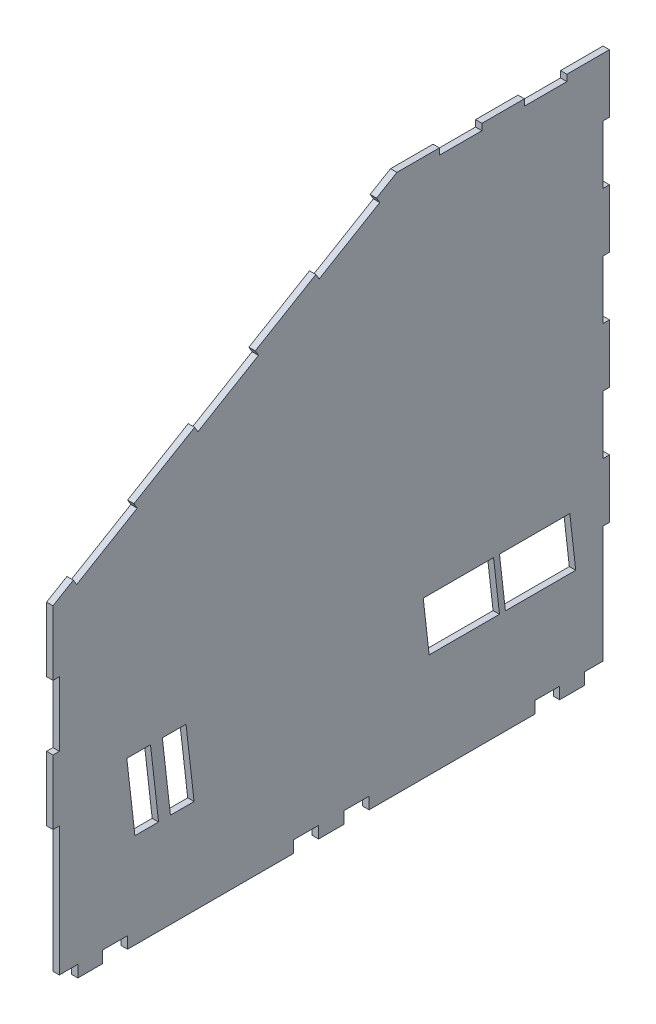
SolidWorks part; units mm, degrees
ref_plane "Ön Düzlem" through (0, 0, 0) normal (0, 0, 1) x (1, 0, 0)
ref_plane "Üst Düzlem" through (0, 0, 0) normal (0, 1, 0) x (1, 0, 0)
ref_plane "Sağ Düzlem" through (0, 0, 0) normal (1, 0, 0) x (0, 0, -1)
sketch "Sketch1" plane through (0, 0, 0) normal (1, 0, 0) x (0, 0, -1)
  line L0 (117.52, 112.5) -> (99.566, 112.5)
  line L13 (-107.0133, -112.5) -> (-107.0133, -114.8)
  line L14 (-6.4686, 92.2661) -> (-32.0795, 77.122)
  line L17 (27.75, 112.5) -> (19.1423, 107.4101)
  line L18 (-114.82, -109.8) -> (-107.0133, -109.8)
  line L20 (-107.0133, -114.8) -> (-96.5067, -114.8)
  line L21 (-86, -112.5) -> (-86, -114.8)
  line L22 (-114.82, -27.96) -> (-114.82, -0.68)
  line L23 (-117.52, -55.24) -> (-117.52, -27.96)
  line L24 (-96.5067, -114.8) -> (-96.5067, -112.5)
  line L25 (-117.52, -0.68) -> (-117.52, 26.6)
  line L26 (-117.52, -0.68) -> (-114.82, -0.68)
  line L27 (-117.52, -27.96) -> (-114.82, -27.96)
  line L28 (-114.82, -82.52) -> (-114.82, -55.24)
  line L29 (-117.52, -55.24) -> (-114.82, -55.24)
  line L31 (-86, -109.8) -> (-86, -112.5)
  line L32 (-107.0133, -109.8) -> (-107.0133, -112.5)
  line L33 (-96.5067, -109.8) -> (-96.5067, -112.5)
  line L34 (-96.5067, -109.8) -> (-86, -109.8)
  line L35 (-5.3333, -112.5) -> (-5.3333, -114.8)
  line L37 (-16, -112.5) -> (-16, -109.8)
  line L38 (-16, -109.8) -> (-5.3333, -109.8)
  line L39 (-5.3333, -114.8) -> (5.3333, -114.8)
  line L40 (-86, -114.8) -> (-16, -114.8)
  line L41 (5.3333, -109.8) -> (16, -109.8)
  line L42 (-5.3333, -109.8) -> (-5.3333, -112.5)
  line L43 (5.3333, -109.8) -> (5.3333, -112.5)
  line L44 (16, -109.8) -> (16, -112.5)
  line L45 (5.3333, -114.8) -> (5.3333, -112.5)
  line L46 (96.5067, -112.5) -> (96.5067, -114.8)
  line L47 (114.82, -35.7) -> (114.82, -11)
  line L48 (86, -109.8) -> (96.5067, -109.8)
  line L49 (96.5067, -114.8) -> (107.0133, -114.8)
  line L51 (86, -109.8) -> (86, -112.5)
  line L52 (96.5067, -109.8) -> (96.5067, -112.5)
  line L53 (107.0133, -109.8) -> (107.0133, -112.5)
  line L55 (107.0133, -109.8) -> (114.82, -109.8)
  line L56 (117.52, -60.4) -> (117.52, -35.7)
  line L57 (114.82, 13.7) -> (114.82, 38.4)
  line L58 (117.52, -11) -> (117.52, 13.7)
  line L59 (114.82, 63.1) -> (114.82, 87.8)
  line L60 (117.52, 38.4) -> (117.52, 63.1)
  line L61 (107.0133, -112.5) -> (107.0133, -114.8)
  line L62 (117.52, 87.8) -> (117.52, 112.5)
  line L63 (114.82, -85.1) -> (114.82, -60.4)
  line L65 (117.52, 13.7) -> (114.82, 13.7)
  line L66 (117.52, 87.8) -> (114.82, 87.8)
  line L67 (117.52, 63.1) -> (114.82, 63.1)
  line L68 (117.52, 38.4) -> (114.82, 38.4)
  line L69 (117.52, -11) -> (114.82, -11)
  line L70 (117.52, -35.7) -> (114.82, -35.7)
  line L71 (117.52, -60.4) -> (114.82, -60.4)
  line L72 (-57.6905, 61.978) -> (-83.3014, 46.8339)
  line L73 (-5.0944, 89.942) -> (-6.4686, 92.2661)
  line L74 (-107.538, 29.3658) -> (-81.9271, 44.5098)
  line L75 (-16, -114.8) -> (-16, -112.5)
  line L76 (99.566, 109.8) -> (81.612, 109.8)
  line L77 (16, -112.5) -> (16, -114.8)
  line L78 (63.658, 109.8) -> (45.704, 109.8)
  line L79 (-108.9123, 31.6899) -> (-117.52, 26.6)
  line L80 (45.704, 109.8) -> (45.704, 112.5)
  line L81 (63.658, 109.8) -> (63.658, 112.5)
  line L82 (81.612, 109.8) -> (81.612, 112.5)
  line L83 (99.566, 109.8) -> (99.566, 112.5)
  line L84 (16, -114.8) -> (86, -114.8)
  line L85 (86, -114.8) -> (86, -112.5)
  line L87 (-108.9123, 31.6899) -> (-107.538, 29.3658)
  line L88 (19.1423, 107.4101) -> (20.5165, 105.086)
  line L89 (-56.3162, 59.6539) -> (-30.7053, 74.7979)
  line L91 (-5.0944, 89.942) -> (20.5165, 105.086)
  line L92 (-30.7053, 74.7979) -> (-32.0795, 77.122)
  line L93 (-56.3162, 59.6539) -> (-57.6905, 61.978)
  line L94 (-81.9271, 44.5098) -> (-83.3014, 46.8339)
  line L95 (45.704, 112.5) -> (27.75, 112.5)
  line L97 (81.612, 112.5) -> (63.658, 112.5)
  line L98 (-114.82, -82.52) -> (-114.82, -109.8)
  line L209 (100.78, -48.8) -> (71.08, -48.8)
  line L211 (100.78, -70.8) -> (73.58, -70.8)
  line L212 (68.58, -48.8) -> (71.08, -70.8)
  line L215 (71.08, -48.8) -> (73.58, -70.8)
  line L216 (41.38, -48.8) -> (38.88, -48.8)
  line L217 (38.88, -48.8) -> (41.38, -70.8)
  line L218 (100.78, -70.8) -> (103.28, -70.8)
  line L219 (100.78, -48.8) -> (103.28, -70.8)
  line L220 (71.08, -70.8) -> (41.38, -70.8)
  line L221 (68.58, -48.8) -> (41.38, -48.8)
  line L226 (-72.9109, -74.8) -> (-76.32, -44.8)
  line L227 (-67.9109, -74.8) -> (-71.32, -44.8)
  line L233 (-82.9109, -74.8) -> (-86.32, -44.8)
  line L235 (-57.9109, -74.8) -> (-61.32, -44.8)
  line L238 (-62.9109, -74.8) -> (-66.32, -44.8) [skipped]
  line L239 (-76.32, -44.8) -> (-86.32, -44.8)
  line L240 (-82.9109, -74.8) -> (-72.9109, -74.8)
  line L241 (-67.9109, -74.8) -> (-57.9109, -74.8)
  line L242 (-71.32, -44.8) -> (-61.32, -44.8)
  line L243 (114.82, -85.1) -> (114.82, -109.8)
  point P0 (0, 0)
  dimension "D1" = 3
extrude "Boss-Extrude1" add sketch "Sketch1" along normal blind 2.7 contours L82 L97 L81 L78 L80 L95 L17 L88 L91 L73 L14 L92 L89 L93 L72 L94 L74 L87 L79 L25 L26 L22 L27 L23 L29 L28 L18 L32 L33 L34 L31 L37 L38 L42 L43 L41 L44 L51 L48 L52 L53 region at (0, -10.0527, -8.4422)
ref_plane "Plane1" through (2.7, 112.5, -27.75) normal (0, -0.509, 0.8608) x (1, 0, 0)
